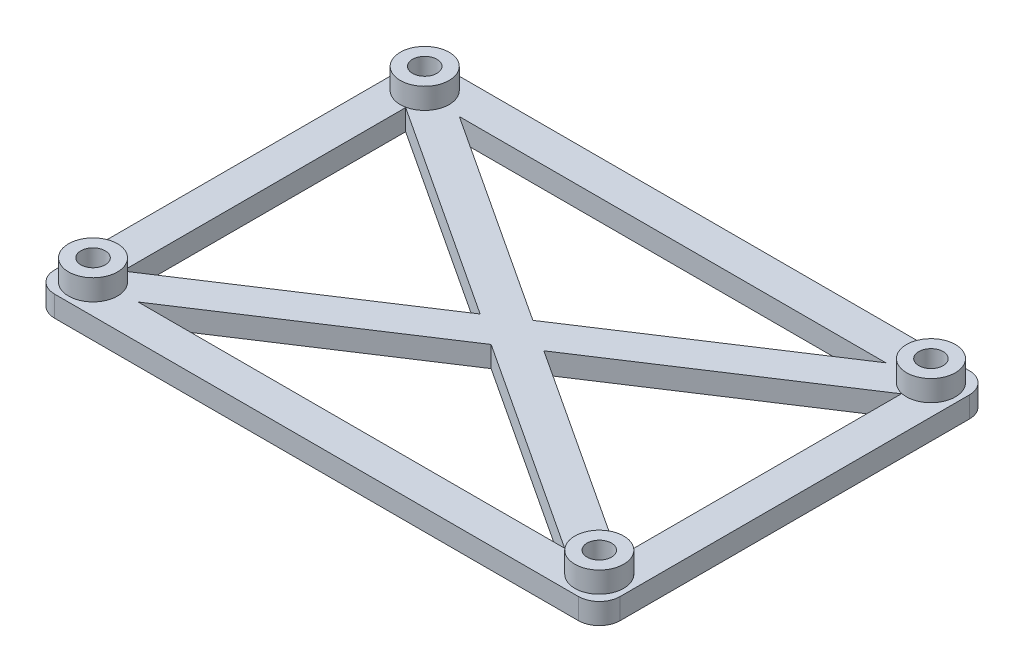
SolidWorks part; units mm, degrees
material "Acrílico (Impacto medio-alto)"
ref_plane "Alzado" through (0, 0, 0) normal (0, 0, 1) x (1, 0, 0)
ref_plane "Planta" through (0, 0, 0) normal (0, 1, 0) x (1, 0, 0)
ref_plane "Vista lateral" through (0, 0, 0) normal (1, 0, 0) x (0, 0, -1)
sketch "Croquis1" plane through (0, 0, 0) normal (0, 1, 0) x (1, 0, 0)
  line L1 (40.5, -28) -> (-40.5, -28)
  line L2 (40.5, -28) -> (40.5, 28)
  line L3 (40.5, 28) -> (-40.5, 28)
  line L4 (-40.5, -28) -> (-40.5, 28)
  line L5 (40.5, -28) -> (-40.5, 28) construction
  line L6 (40.5, 28) -> (-40.5, -28) construction
  point P0 (0, 0)
  dimension "D1" = 81
  dimension "D2" = 56
extrude "Saliente-Extruir1" add sketch "Croquis1" along normal blind 3
sketch "Croquis3" plane through (0, 0, 0) normal (0, -1, 0) x (1, 0, 0)
  circle A0 centre (-36.25, 23.75) radius 1.75
  circle A1 centre (-36.25, -23.75) radius 1.75
  circle A2 centre (36.25, -23.75) radius 1.75
  circle A3 centre (36.25, 23.75) radius 1.75
  dimension "D1" = 3.5
extrude "Cortar-Extruir2" cut sketch "Croquis3" against normal through all
sketch "Croquis4" plane through (0, 3, 0) normal (0, 1, 0) x (1, 0, 0)
  circle A1 centre (-36.25, 23.75) radius 1.75 construction
  circle A3 centre (-36.25, 23.75) radius 1.75
  circle A4 centre (-36.25, 23.75) radius 3.5
  dimension "D1" = 7
extrude "Saliente-Extruir2" add sketch "Croquis4" along normal blind 3
mirror "Simetría1" about plane through (0, 0, 0) normal (0, 0, 1) of "Saliente-Extruir2"
mirror "Simetría2" about plane through (0, 0, 0) normal (1, 0, 0) of "Simetría1"
fillet "Redondeo1" radius 3 4 edges at (40.5, 1.5, -28) (40.5, 1.5, 28) (-40.5, 1.5, 28) (-40.5, 1.5, -28)
sketch "Croquis5" plane through (0, 0, 0) normal (0, -1, 0) x (1, 0, 0)
  line L0 (-36.25, 23.75) -> (36.25, -23.75) construction
  line L1 (36.25, 23.75) -> (-36.25, -23.75) construction
  line L2 (-35.5, 20.2698) -> (-4.5618, 0)
  line L3 (30.5434, 23) -> (0, 2.9888)
  line L4 (-30.5434, 23) -> (0, 2.9888)
  line L5 (35.5, 20.2698) -> (4.5618, 0)
  line L8 (-4.5618, 0) -> (-35.5, -20.2698)
  line L9 (4.5618, 0) -> (35.5, -20.2698)
  line L11 (0, -2.9888) -> (30.5434, -23)
  line L12 (0, -2.9888) -> (-30.5434, -23)
  line L15 (-37.5, 28) -> (37.5, 28) construction
  line L16 (-40.5, -25) -> (-40.5, 25) construction
  line L17 (34.8799, 25.8412) -> (-37.6201, -21.6588) construction
  line L18 (37.5, -28) -> (-37.5, -28) construction
  line L19 (40.5, 25) -> (40.5, -25) construction
  line L21 (35.5, 20.2698) -> (35.5, -20.2698)
  line L22 (37.6201, 21.6588) -> (-34.8799, -25.8412) construction
  line L23 (-34.8799, 25.8412) -> (37.6201, -21.6588) construction
  line L25 (-37.6201, 21.6588) -> (34.8799, -25.8412) construction
  line L26 (30.5434, -23) -> (-30.5434, -23)
  line L28 (-35.5, -20.2698) -> (-35.5, 20.2698)
  line L29 (-30.5434, 23) -> (30.5434, 23)
  dimension "D3" = 5
  dimension "D4" = 5
  dimension "D5" = 5
  dimension "D6" = 5
  dimension "D1" = 2.5
  dimension "D2" = 2.5
extrude "Cortar-Extruir3" cut sketch "Croquis5" against normal through all
